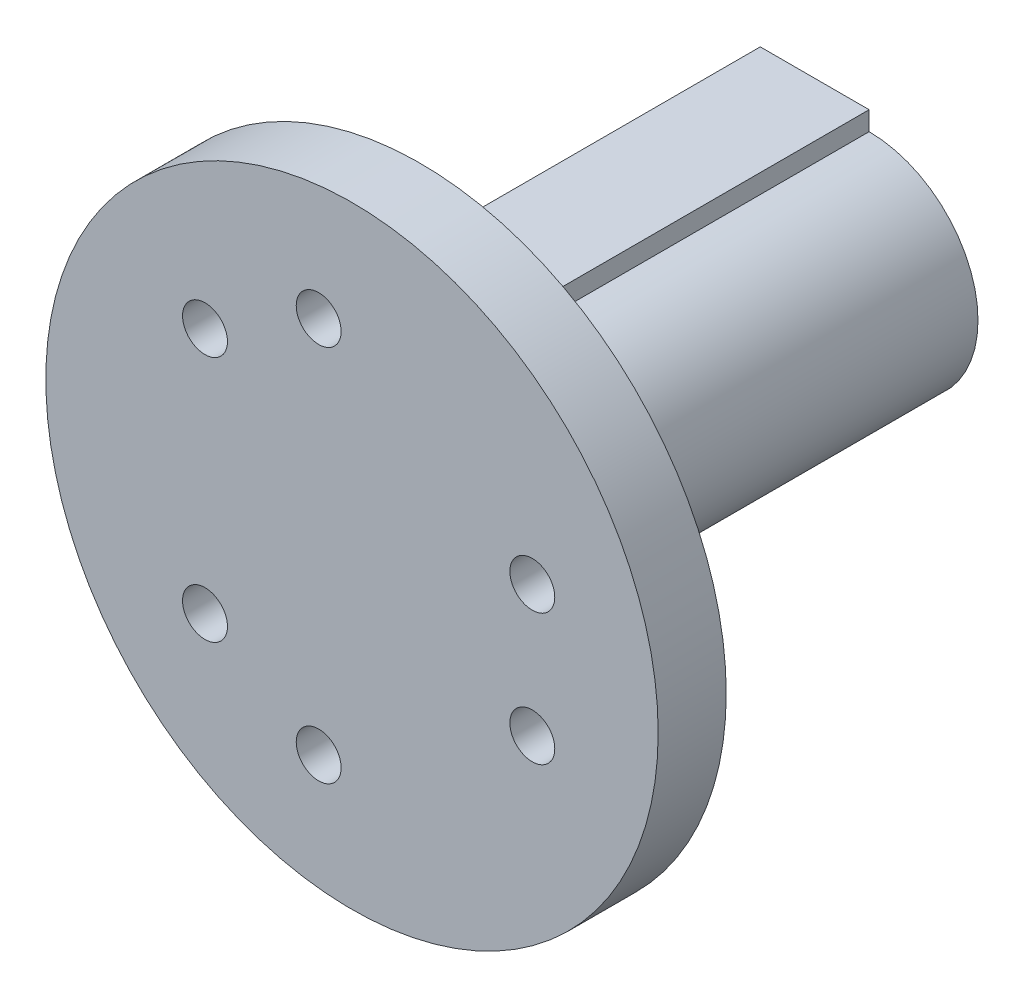
SolidWorks part; units mm, degrees
ref_plane "정면" through (0, 0, 0) normal (0, 0, 1) x (1, 0, 0)
ref_plane "윗면" through (0, 0, 0) normal (0, 1, 0) x (1, 0, 0)
ref_plane "우측면" through (0, 0, 0) normal (1, 0, 0) x (0, 0, -1)
sketch "스케치1" plane through (0, 0, 0) normal (0, 0, 1) x (1, 0, 0)
  line L0 (0, 0) -> (0, 22.5) construction
  line L1 (0, 0) -> (-3.9071, 22.1582) construction
  line L2 (0, 0) -> (-17.236, 14.4627) construction
  circle A0 centre (0, 0) radius 22.5
  circle A1 centre (0, 0) radius 14.1 construction
  circle A2 centre (-2.4484, 13.8858) radius 1.65
  circle A3 centre (-10.8012, 9.0633) radius 1.65
  circle A4 centre (13.2497, 4.8225) radius 1.65
  circle A5 centre (13.2497, -4.8225) radius 1.65
  circle A6 centre (-2.4484, -13.8858) radius 1.65
  circle A7 centre (-10.8012, -9.0633) radius 1.65
  point P22 (0, 0)
  dimension "D1" = 45
  dimension "D2" = 28.2
  dimension "D5" = 3.3
  dimension "D3" = 10
  dimension "D4" = 40
  dimension "D6" = 3
extrude "보스-돌출1" add sketch "스케치1" along normal blind 5
sketch "스케치3" plane through (0, 0, 0) normal (0, 0, -1) x (-1, 0, 0)
  circle A0 centre (2.4484, 13.8858) radius 3
  circle A1 centre (10.8012, 9.0633) radius 3
  circle A2 centre (10.8012, -9.0633) radius 3
  circle A3 centre (2.4484, -13.8858) radius 3
  circle A4 centre (-13.2497, -4.8225) radius 3
  circle A5 centre (-13.2497, 4.8225) radius 3
  dimension "D1" = 6
extrude "컷-돌출1" cut sketch "스케치3" against normal blind 2
sketch "스케치11" plane through (0, 0, 0) normal (0, 0, -1) x (-1, 0, 0)
  circle A0 centre (0, 0) radius 8
extrude "보스-돌출2" add sketch "스케치11" along normal blind 25 contours A0
sketch "스케치12" plane through (0, 0, 0) normal (0, 1, 0) x (1, 0, 0)
  line L0 (-8, 25) -> (-8, 0) construction
  line L1 (0, 25) -> (-8, 25)
  line L2 (0, 25) -> (0, 10)
  line L3 (0, 10) -> (-8, 10)
  line L4 (-8, 25) -> (-8, 10)
  line L5 (8, 25) -> (-8, 25) construction
extrude "컷-돌출9" cut sketch "스케치12" against normal blind 25 and the other way blind 25
sketch "스케치13" plane through (0, 0, 0) normal (-1, 0, 0) x (0, 0, 1)
  line L0 (-25, 0) -> (-25, -9.4) construction
  line L1 (-25, -8) -> (-25, 8) construction
  line L2 (-25, 0) -> (-25, 9.4) construction
  line L3 (-10, 0) -> (-10, -9.4) construction
  line L4 (-10, 8) -> (-10, -8) construction
  line L5 (-10, 0) -> (-10, 9.4) construction
  line L7 (-25, -9.4) -> (-10, -9.4)
  line L8 (-25, -9.4) -> (-25, 9.4)
  line L9 (-25, 9.4) -> (-10, 9.4)
  line L10 (-10, -9.4) -> (-10, 9.4)
  dimension "D1" = 9.4
  dimension "D2" = 9.4
extrude "보스-돌출3" add sketch "스케치13" along normal blind 8
sketch "스케치15" plane through (0, 0, -25) normal (0, 0, -1) x (-1, 0, 0)
  line L0 (0, 8) -> (0, 9.4)
  line L1 (0, -9.4) -> (8, -9.4)
  line L2 (0, -9.4) -> (0, -8)
  line L3 (0, 9.4) -> (8, 9.4)
  line L4 (8, -9.4) -> (8, 9.4)
  arc A0 (0, 8) -> (0, -8) centre (0, 0) ccw
extrude "보스-돌출5" add sketch "스케치15" along normal blind 8
